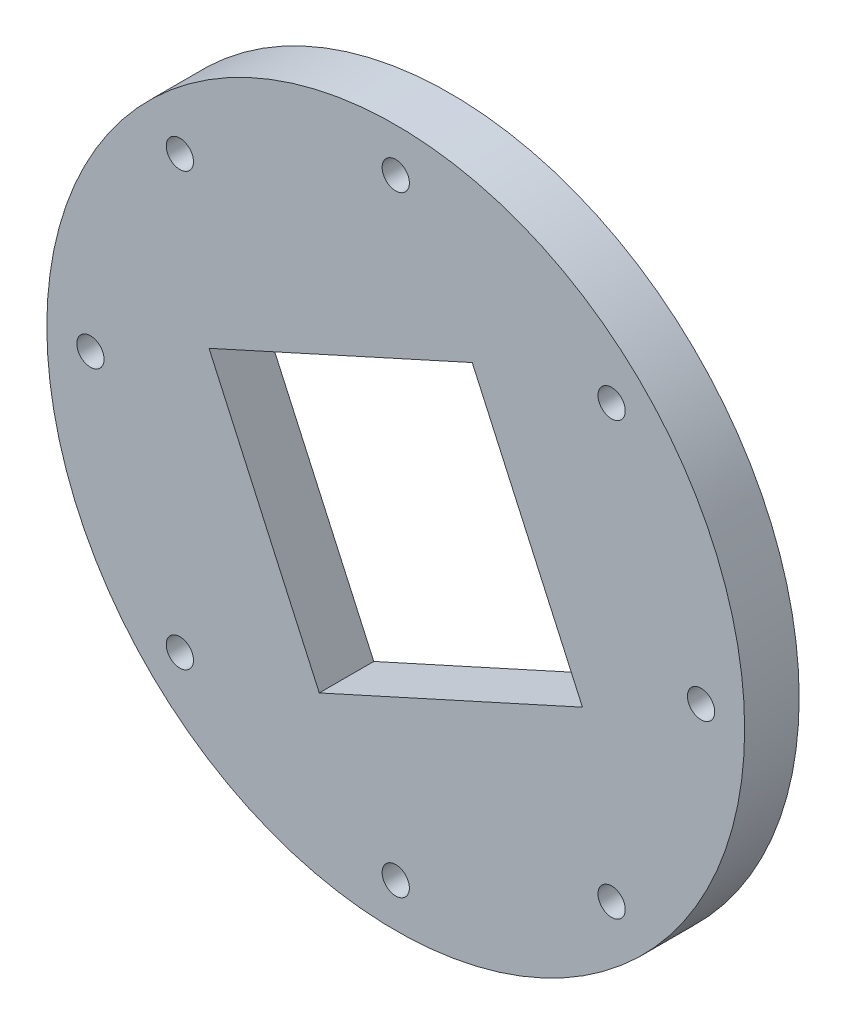
SolidWorks part; units mm, degrees
ref_plane "Alzado" through (0, 0, 0) normal (0, 0, 1) x (1, 0, 0)
ref_plane "Planta" through (0, 0, 0) normal (0, 1, 0) x (1, 0, 0)
ref_plane "Vista lateral" through (0, 0, 0) normal (1, 0, 0) x (0, 0, -1)
sketch "Croquis1" plane through (0, 0, 0) normal (0, 0, 1) x (1, 0, 0)
  circle A0 centre (0, 0) radius 32
  dimension "D1" = 64
extrude "Saliente-Extruir1" add sketch "Croquis1" along normal blind 5
sketch "Croquis2" plane through (0, 0, 5) normal (0, 0, 1) x (1, 0, 0)
  line L0 (0, 0) -> (0, 28) construction
  line L1 (0, 0) -> (19.799, 19.799) construction
  line L2 (0, 0) -> (28, 0) construction
  line L3 (0, 0) -> (19.799, -19.799) construction
  line L4 (0, 0) -> (0, -28) construction
  line L5 (0, 0) -> (-19.799, -19.799) construction
  line L6 (0, 0) -> (-28, 0) construction
  line L7 (0, 0) -> (-19.799, 19.799) construction
  circle A0 centre (0, 28) radius 1.25
  circle A1 centre (0, 0) radius 32 construction
  circle A2 centre (19.799, 19.799) radius 1.25
  circle A3 centre (28, 0) radius 1.25
  circle A4 centre (19.799, -19.799) radius 1.25
  circle A5 centre (0, -28) radius 1.25
  circle A6 centre (-19.799, -19.799) radius 1.25
  circle A7 centre (-28, 0) radius 1.25
  circle A8 centre (-19.799, 19.799) radius 1.25
  point P19 (0, 0)
  dimension "D1" = 2.5
  dimension "D2" = 28
  dimension "D3" = 8
extrude "Cortar-Extruir1" cut sketch "Croquis2" against normal through all
sketch "Croquis3" plane through (0, 0, 5) normal (0, 0, 1) x (1, 0, 0)
  line L0 (0, 32) -> (0, -32) construction
  line L1 (17.1246, -5.6897) -> (-7.0133, -16.6265)
  line L2 (17.1246, -5.6897) -> (7.0133, 16.6265)
  line L3 (7.0133, 16.6265) -> (-17.1246, 5.6897)
  line L4 (-7.0133, -16.6265) -> (-17.1246, 5.6897)
  line L5 (17.1246, -5.6897) -> (-17.1246, 5.6897) construction
  line L6 (7.0133, 16.6265) -> (-7.0133, -16.6265) construction
  circle A0 centre (0, 0) radius 32 construction
  point P0 (0, 0)
  dimension "D1" = 24.5
  dimension "D2" = 26.5
  dimension "D3" = 114.375
extrude "Cortar-Extruir2" cut sketch "Croquis3" against normal blind 10
